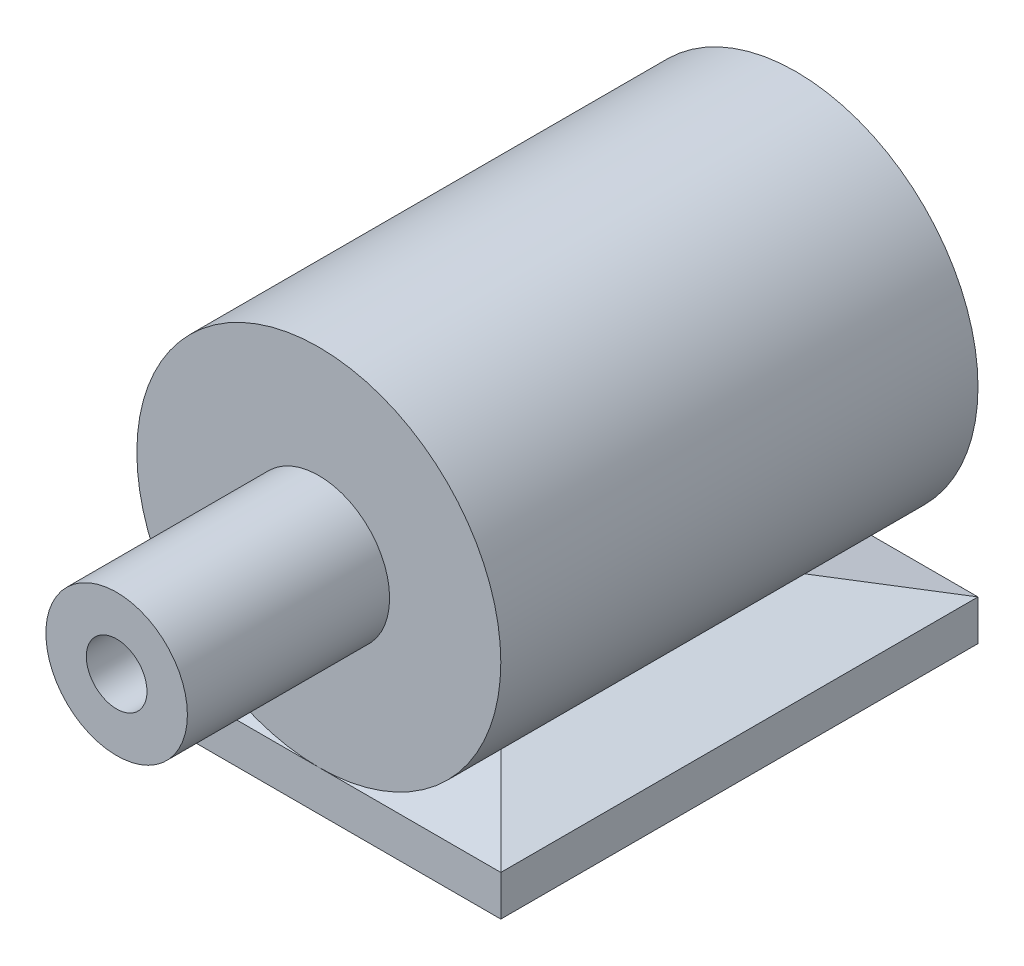
SolidWorks part; units mm, degrees
ref_plane "Front Plane" through (0, 0, 0) normal (0, 0, 1) x (1, 0, 0)
ref_plane "Top Plane" through (0, 0, 0) normal (0, 1, 0) x (1, 0, 0)
ref_plane "Right Plane" through (0, 0, 0) normal (1, 0, 0) x (0, 0, -1)
sketch "Sketch1" plane through (0, 0, 0) normal (0, 0, 1) x (1, 0, 0)
  circle A0 centre (0, 0) radius 45
  dimension "D1" = 90
extrude "Boss-Extrude1" add sketch "Sketch1" along normal blind 118
sketch "Sketch2" plane through (0, 0, 118) normal (0, 0, 1) x (1, 0, 0)
  circle A0 centre (0, 0) radius 7.5
  circle A1 centre (0, 0) radius 17.5
  dimension "D2" = 15
  dimension "D1" = 10
extrude "Boss-Extrude2" add sketch "Sketch2" along normal blind 50
ref_plane "Plane1" through (0, -45, 0) normal (0, -1, 0) x (-1, 0, 0)
sketch "Sketch3" plane through (0, -45, 0) normal (0, -1, 0) x (-1, 0, 0)
  line L1 (45, 0) -> (-45, 0)
  line L2 (45, 0) -> (45, -118)
  line L3 (45, -118) -> (-45, -118)
  line L4 (-45, 0) -> (-45, -118)
extrude "Boss-Extrude3" add sketch "Sketch3" along normal blind 10
extrude "Boss-Extrude4" add sketch "Sketch3<2>" along normal mid plane 12 draft 77
sketch "Sketch3<2>" plane through (0, -45, 0) normal (0, -1, 0) x (-1, 0, 0) same geometry as "Sketch3"
